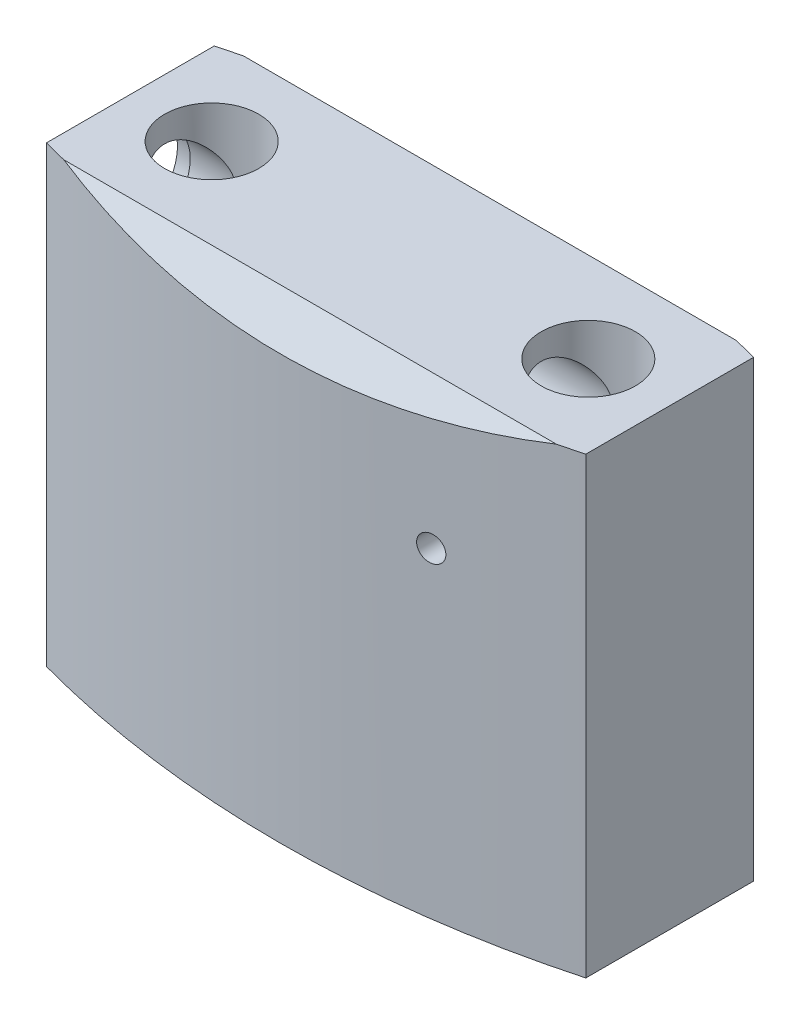
SolidWorks part; units mm, degrees
ref_plane "前视基准面" through (0, 0, 0) normal (0, 0, 1) x (1, 0, 0)
ref_plane "上视基准面" through (0, 0, 0) normal (0, 1, 0) x (1, 0, 0)
ref_plane "右视基准面" through (0, 0, 0) normal (1, 0, 0) x (0, 0, -1)
other "Configuration Table"
sketch "草图2" plane through (0, 0, 0) normal (0, 1, 0) x (1, 0, 0)
  line L0 (-60.5244, 0) -> (-41.7534, 0) construction
  line L1 (-31.5, 9.7918) -> (31.5, 9.7918)
  line L2 (-31.5, 9.7918) -> (-31.5, -9.7918)
  line L3 (-31.5, -9.7918) -> (31.5, -9.7918)
  line L4 (31.5, 9.7918) -> (31.5, -9.7918)
  line L5 (-31.5, 9.7918) -> (31.5, -9.7918) construction
  line L6 (-31.5, -9.7918) -> (31.5, 9.7918) construction
  arc A0 (-31.5, 9.7918) -> (31.5, 9.7918) centre (0, -106) cw
  arc A1 (-31.5, -9.7918) -> (31.5, -9.7918) centre (0, 106) ccw
  point P0 (0, 0)
  point P8 (0, 14)
  dimension "D1" = 120
  dimension "D2" = 14
  dimension "D3" = 63
extrude "凸台-拉伸1" add sketch "草图2" along normal blind 53 contours L3 A1 | A0 L1 | L4 L1 L2 L3 region at (0, 0, -11.4777) region at (0, 0, 0) region at (0, 0, 11.4777)
sketch "草图3" plane through (31.5, 0, 0) normal (1, 0, 0) x (0, 0, -1)
  line L3 (-14, 53) -> (-10.5, 53)
  line L4 (-14, 53) -> (-14, 49.5)
  line L5 (-14, 53) -> (-14, 0) construction
  line L6 (-14, 49.5) -> (-10.5, 53)
  line L7 (0, 56.4934) -> (0, 47.0319) construction
  line L8 (14, 53) -> (14, 49.5)
  line L9 (14, 53) -> (10.5, 53)
  line L10 (14, 49.5) -> (10.5, 53)
  dimension "D1" = 3.5
extrude "切除-拉伸1" cut sketch "草图3" against normal through all both and the other way through all
sketch "草图4" plane through (0, 53, 0) normal (0, 1, 0) x (1, 0, 0)
  line L0 (0, 10.5) -> (0, -20.3921) construction
  line L1 (-28.7706, 10.5) -> (28.7706, 10.5) construction
  line L2 (-31.5, 0) -> (35.8673, 0) construction
  line L3 (-31.5, 9.7918) -> (-31.5, -9.7918) construction
  circle A0 centre (22, 0) radius 5.5
  circle A1 centre (22, 0) radius 1
  circle A2 centre (-22, 0) radius 5.5
  dimension "D2" = 11
  dimension "D3" = 2
  dimension "D1" = 22
extrude "切除-拉伸2" cut sketch "草图4" against normal blind 14 and the other way through all contours A2
extrude "切除-拉伸3" cut sketch "草图4<3>" against normal blind 45 contours A0
sketch "草图4<3>" plane through (0, 53, 0) normal (0, 1, 0) x (1, 0, 0) same geometry as "草图4"
extrude "切除-拉伸4" cut sketch "草图4<4>" against normal through all from offset 45 contours A1
sketch "草图4<4>" plane through (0, 53, 0) normal (0, 1, 0) x (1, 0, 0) same geometry as "草图4"
sketch "草图5" plane through (-31.5, 0, 0) normal (-1, 0, 0) x (0, 0, 1)
  line L0 (5.5, 53) -> (-5.5, 53) construction
  circle A0 centre (0, 45) radius 5
  circle A1 centre (0, 45) radius 5.5
  dimension "D2" = 11
  dimension "D3" = 10
  dimension "D1" = 8
extrude "切除-拉伸5" cut sketch "草图5" against normal blind 2 contours A1
extrude "切除-拉伸6" cut sketch "草图5<3>" against normal up to surface (51.2087 mm away) contours A0 up to face at (22, 8, 5.5)
sketch "草图5<3>" plane through (-31.5, 0, 0) normal (-1, 0, 0) x (0, 0, 1) same geometry as "草图5"
sketch "草图7" plane through (0, 0, 0) normal (0, -1, 0) x (1, 0, 0)
  circle A0 centre (0, 0) radius 9
  circle A1 centre (0, 0) radius 7
  dimension "D1" = 18
  dimension "D2" = 14
extrude "切除-拉伸7" cut sketch "草图7" against normal blind 1
sketch "草图9" plane through (0, 0, 0) normal (0, -1, 0) x (1, 0, 0)
  circle A1 centre (0, 0) radius 7
  circle A2 centre (0, 0) radius 7
  dimension "D1" = 0
extrude "切除-拉伸9" cut sketch "草图9" against normal blind 2
sketch "草图10" plane through (0, 2, 0) normal (0, -1, 0) x (1, 0, 0)
  circle A0 centre (0, 0) radius 6
  dimension "D1" = 12
extrude "切除-拉伸10" cut sketch "草图10" against normal blind 42
sketch "草图11" plane through (0, 0, 0) normal (0, 0, 1) x (1, 0, 0)
  line L0 (-31.5, 53) -> (35.8673, 53) construction
  circle A0 centre (16.5, 37.5) radius 1.5
  dimension "D3" = 3
  dimension "D1" = 16.5
  dimension "D2" = 15.5
extrude "切除-拉伸11" cut sketch "草图11" against normal through all both and the other way through all
sketch "草图12" plane through (-31.5, 0, 0) normal (-1, 0, 0) x (0, 0, 1)
  line L0 (0, 0) -> (0, 35.6528) construction
  line L2 (-9, 0) -> (9, 0) construction
  circle A1 centre (0, 28.6) radius 1.6
  circle A2 centre (0, 24.6) radius 1.6
  circle A3 centre (0, 20.6) radius 1.6
  circle A4 centre (0, 16.6) radius 1.6
  circle A5 centre (0, 12.6) radius 1.6
  circle A6 centre (0, 8.6) radius 1.6
  circle A7 centre (0, 4.6) radius 1.6
  dimension "D1" = 3.2
  dimension "D2" = 28.6
  dimension "D3" = 7
extrude "切除-拉伸16" cut sketch "草图12" against normal blind 1.5
sketch "草图17" plane through (-30, 0, 0) normal (-1, 0, 0) x (0, 0, 1)
  circle A0 centre (0, 28.6) radius 1.5
  circle A1 centre (0, 24.6) radius 1.5
  circle A2 centre (0, 20.6) radius 1.5
  circle A3 centre (0, 16.6) radius 1.5
  circle A4 centre (0, 12.6) radius 1.5
  circle A5 centre (0, 8.6) radius 1.5
  circle A6 centre (0, 4.6) radius 1.5
  dimension "D1" = 3
  dimension "D2" = 7
extrude "切除-拉伸17" cut sketch "草图17" against normal up to next
